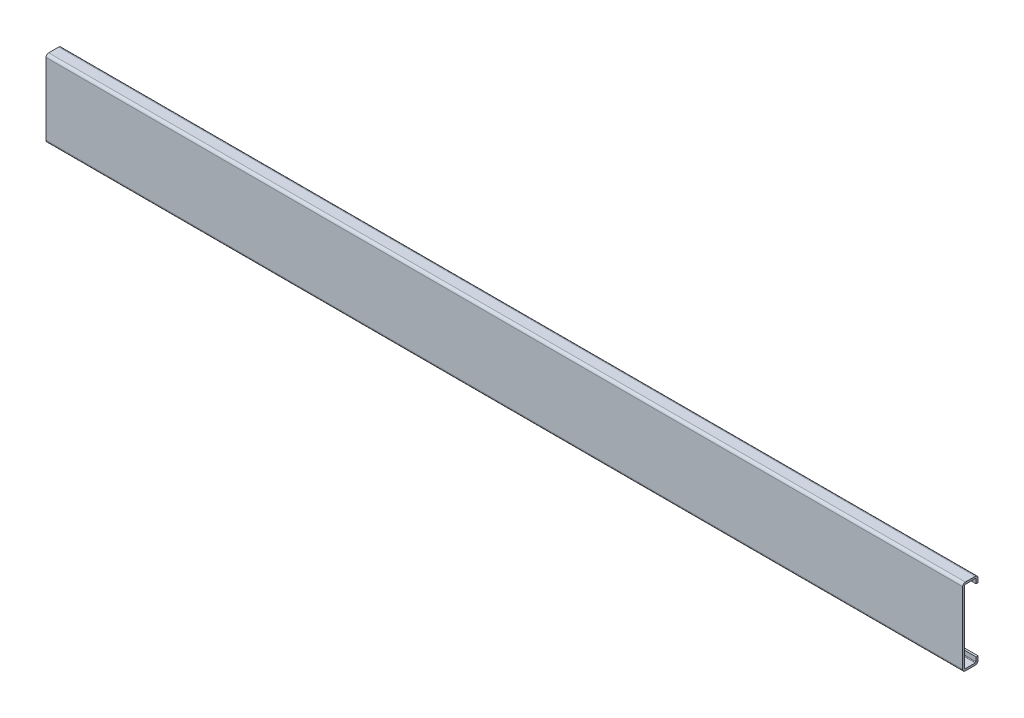
SolidWorks part; units mm, degrees
ref_plane "Спереди" through (0, 0, 0) normal (0, 0, 1) x (1, 0, 0)
ref_plane "Сверху" through (0, 0, 0) normal (0, 1, 0) x (1, 0, 0)
ref_plane "Справа" through (0, 0, 0) normal (1, 0, 0) x (0, 0, -1)
sketch "Эскиз1" plane through (0, 0, 0) normal (1, 0, 0) x (0, 0, -1)
  line L0 (0, -21.5) -> (0, 21.5)
  line L1 (-12.4481, 0) -> (26.4522, 0) construction
  line L2 (1, 22.5) -> (7, 22.5)
  line L3 (8, 21.5) -> (8, 19)
  line L4 (8, -21.5) -> (8, -19)
  line L5 (1, -22.5) -> (7, -22.5)
  arc A0 (7, 22.5) -> (8, 21.5) centre (7, 21.5) cw
  arc A1 (0, 21.5) -> (1, 22.5) centre (1, 21.5) cw
  arc A2 (0, -21.5) -> (1, -22.5) centre (1, -21.5) ccw
  arc A3 (7, -22.5) -> (8, -21.5) centre (7, -21.5) ccw
  point P19 (0, 0)
  dimension "D1" = 1
extrude "Вытянуть-Тонкостенный1" add sketch "Эскиз1" along normal blind 550 thin thin type mid plane wall 1.2
